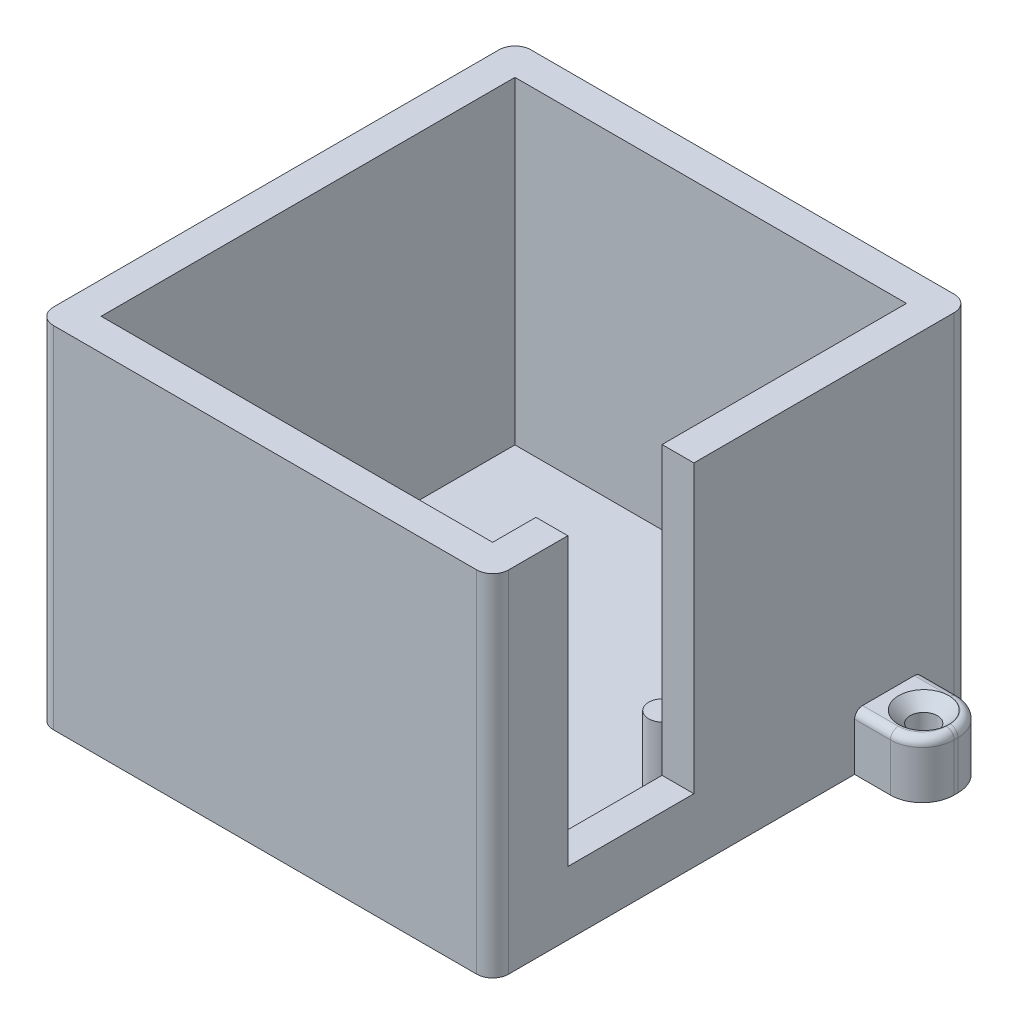
SolidWorks part; units mm, degrees
material "Plastique personnalisé"
ref_plane "Plan de face" through (0, 0, 0) normal (0, 0, 1) x (1, 0, 0)
ref_plane "Plan de dessus" through (0, 0, 0) normal (0, 1, 0) x (1, 0, 0)
ref_plane "Plan de droite" through (0, 0, 0) normal (1, 0, 0) x (0, 0, -1)
sketch "Esquisse1" plane through (0, 0, 0) normal (0, 1, 0) x (1, 0, 0)
  line L1 (-24.6, -26) -> (24.6, -26)
  line L2 (-24.6, -26) -> (-24.6, 26)
  line L3 (-24.6, 26) -> (24.6, 26)
  line L4 (24.6, -26) -> (24.6, 26)
  line L5 (-24.6, -26) -> (24.6, 26) construction
  line L6 (-24.6, 26) -> (24.6, -26) construction
  point P0 (0, 0)
  dimension "D1" = 52
  dimension "D2" = 49.2
extrude "Boss.-Extru.1" add sketch "Esquisse1" along normal blind 40
shell "Coque1" thickness 4 removed face at (0, 40, 0) outward yes
fillet "Congé1" radius 2 1 edges at (28.6, 18, 30)
fillet "Congé2" radius 2 1 edges at (28.6, 18, -30)
fillet "Congé3" radius 2 1 edges at (-28.6, 18, -30)
fillet "Congé4" radius 2 1 edges at (-28.6, 18, 30)
sketch "Esquisse5" plane through (0, 0, 0) normal (0, 1, 0) x (1, 0, 0)
  circle A4 centre (-22.6, -2.6) radius 1.8
  circle A5 centre (22.6, -2.6) radius 1.8
  circle A6 centre (-22.6, -24) radius 1.8
  circle A7 centre (22.6, -24) radius 1.8
extrude "Boss.-Extru.2" add sketch "Esquisse5" along normal blind 9
sketch "Esquisse9" plane through (0, 40, 0) normal (0, 1, 0) x (1, 0, 0)
  line L0 (28.6, -28) -> (28.6, 28) construction
  line L1 (28.6, -4.715) -> (24.6, -4.715)
  line L2 (28.6, -4.715) -> (28.6, -20.5588)
  line L3 (28.6, -20.5588) -> (24.6, -20.5588)
  line L4 (24.6, -4.715) -> (24.6, -20.5588)
  line L5 (24.6, -26) -> (24.6, 26) construction
extrude "Enlèv. mat.-Extru.3" cut sketch "Esquisse9" against normal blind 36
ref_plane "Plan1" through (0, 9, 0) normal (0, 1, 0) x (1, 0, 0)
sketch "Esquisse11" plane through (0, -4, 0) normal (0, -1, 0) x (-1, 0, 0)
  line L0 (28.6, 28) -> (28.6, -13.3608) construction
  line L1 (28.6, 15.4822) -> (37.1, 15.4822)
  line L2 (28.6, 15.4822) -> (28.6, 23.9822)
  line L3 (28.6, 23.9822) -> (37.1, 23.9822)
  line L4 (37.1, 15.4822) -> (37.1, 23.9822)
  line L5 (-28.6, -13.3608) -> (-28.6, 28) construction
  line L6 (-28.6, 15.4822) -> (-37.1, 15.4822)
  line L7 (-28.6, 15.4822) -> (-28.6, 23.9822)
  line L8 (-28.6, 23.9822) -> (-37.1, 23.9822)
  line L9 (-37.1, 15.4822) -> (-37.1, 23.9822)
  dimension "D1" = 8.5
  dimension "D2" = 8.5
  dimension "D3" = 8.5
  dimension "D4" = 8.5
extrude "Boss.-Extru.4" add sketch "Esquisse11" against normal blind 7
fillet "Congé5" radius 4 2 edges at (37.1, -0.5, -15.4822) (37.1, -0.5, -23.9822)
fillet "Congé6" radius 4 2 edges at (-37.1, -0.5, -23.9822) (-37.1, -0.5, -15.4822)
fillet "Congé7" radius 1 5 edges at (-37.1, 3, -19.7322) (-30.85, 3, -23.9822) (-35.9284, 3, -22.8107) (-35.9284, 3, -16.6538) (-30.85, 3, -15.4822)
fillet "Congé8" radius 1 5 edges at (30.85, 3, -15.4822) (35.9284, 3, -16.6538) (37.1, 3, -19.7322) (35.9284, 3, -22.8107) (30.85, 3, -23.9822)
hole_wizard "Fraisage pour vis à tête fraisée M31" positions "Esquisse17" profile "Esquisse16" countersink size "M3" standard "ISO" end condition through all
sketch "Esquisse17" plane through (0, 3, 0) normal (0, 1, 0) x (1, 0, 0)
  point P0 (-32.9046, 19.8257)
  point P2 (32.9408, 19.8257)
sketch "Esquisse16" plane through (-32.9046, 3, -19.8257) normal (1, 0, 0) x (0, 0, 1)
  line L0 (0, 0) -> (0, 7)
  line L1 (0, 7) -> (1.7, 7)
  line L2 (1.7, 7) -> (1.7, 1.45)
  line L3 (1.7, 1.45) -> (3.15, 0)
  line L5 (3.15, 0) -> (0, 0)
  line L6 (-1.7, 1.45) -> (-3.15, 0) construction
  line L11 (0, -6.35) -> (0, 107.95) construction
  dimension "Diamètre du perçage jusqu'au prochain" = 3.4
  dimension "Profondeur du perçage jusqu'au prochain" = 7
  dimension "Diamètre du fraisage entrant" = 6.3
  dimension "Angle du fraisage entrant" = 90
